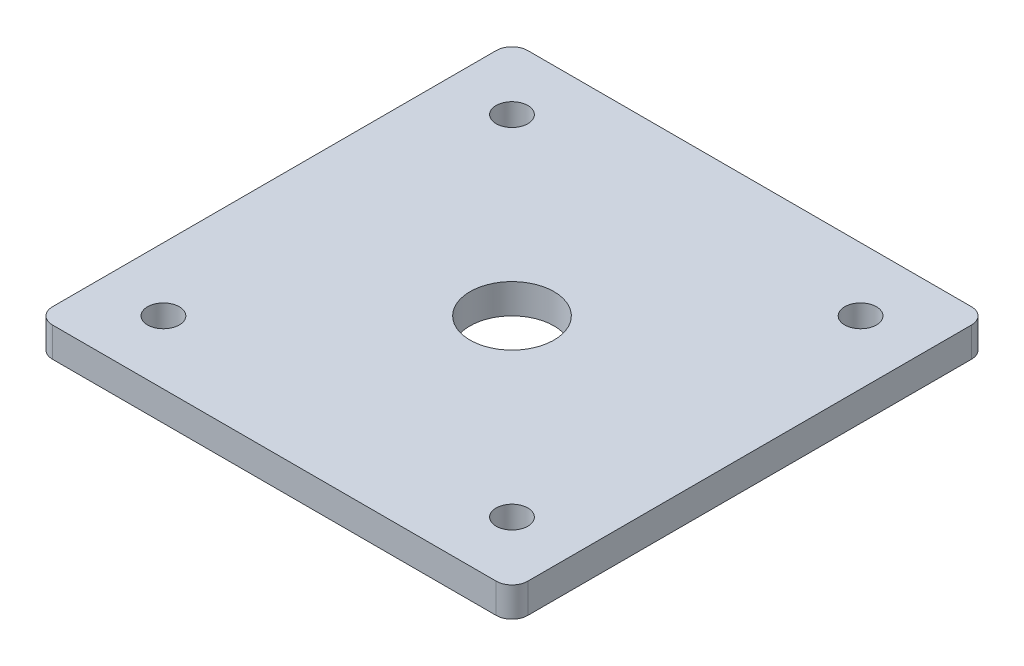
SolidWorks part; units mm, degrees
material "Acrylic (Medium-high impact)"
ref_plane "Front" through (0, 0, 0) normal (0, 0, 1) x (1, 0, 0)
ref_plane "Top" through (0, 0, 0) normal (0, 1, 0) x (1, 0, 0)
ref_plane "Right" through (0, 0, 0) normal (1, 0, 0) x (0, 0, -1)
sketch "Sketch1" plane through (0, 0, 0) normal (0, 0, 1) x (1, 0, 0)
  line L0 (-22.225, 0) -> (22.225, 0)
  dimension "D1" = 44.45
sketch "Sketch2" plane through (0, 0, 0) normal (0, 1, 0) x (1, 0, 0)
  line L0 (-13.97, 13.97) -> (13.97, 13.97) construction
  line L1 (-13.97, 13.97) -> (-13.97, -13.97) construction
  line L2 (-13.97, -13.97) -> (13.97, -13.97) construction
  line L3 (13.97, 13.97) -> (13.97, -13.97) construction
  line L4 (-13.97, 13.97) -> (13.97, -13.97) construction
  line L5 (-13.97, -13.97) -> (13.97, 13.97) construction
  line L7 (-19.05, 19.05) -> (19.05, 19.05)
  line L8 (-19.05, 19.05) -> (-19.05, -19.05)
  line L9 (-19.05, -19.05) -> (19.05, -19.05)
  line L10 (19.05, 19.05) -> (19.05, -19.05)
  line L11 (-19.05, 19.05) -> (19.05, -19.05) construction
  line L12 (-19.05, -19.05) -> (19.05, 19.05) construction
  circle A0 centre (-13.97, 13.97) radius 1.27
  circle A1 centre (-13.97, -13.97) radius 1.27
  circle A2 centre (13.97, -13.97) radius 1.27
  circle A3 centre (13.97, 13.97) radius 1.27
  circle A4 centre (0, 0) radius 3.3655
  point P0 (0, 0)
  point P12 (0, 0)
  dimension "D3" = 2.54
  dimension "D5" = 6.731
  dimension "D1" = 27.94
  dimension "D2" = 27.94
  dimension "D4" = 38.1
extrude "Boss-Extrude1" add sketch "Sketch2" along normal blind 2.3813
fillet "Fillet1" radius 1.27 4 edges at (-19.05, 1.1906, -19.05) (19.05, 1.1906, -19.05) (19.05, 1.1906, 19.05) (-19.05, 1.1906, 19.05)
pattern_linear "LPattern1" [suppressed] count 2 spacing 44.45 count 4 spacing 44.45 of bodies 188
